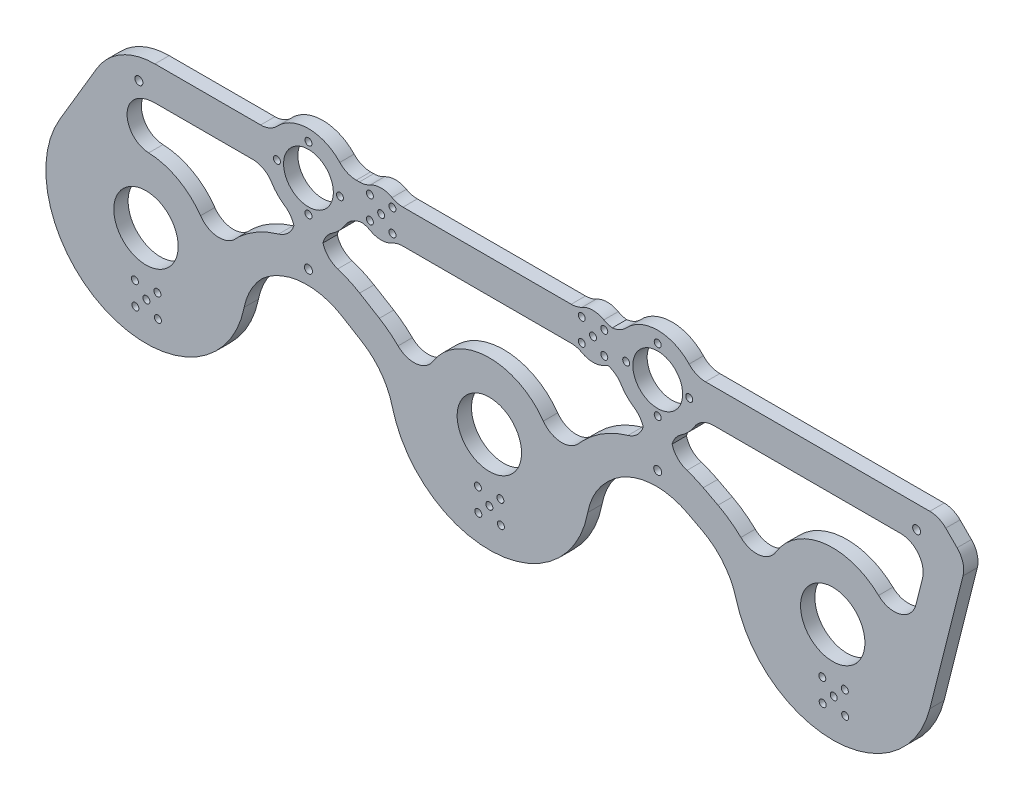
SolidWorks part; units mm, degrees
note: The reader was unsure of these and kept them because the rebuilt part matched: shared geometry of "Sketch7<4>", "Sketch10<4>".
ref_plane "Front Plane" through (0, 0, 0) normal (0, 0, 1) x (1, 0, 0)
ref_plane "Top Plane" through (0, 0, 0) normal (0, 1, 0) x (1, 0, 0)
ref_plane "Right Plane" through (0, 0, 0) normal (1, 0, 0) x (0, 0, -1)
sketch "Sketch1" plane through (0, 0, 0) normal (0, 0, 1) x (1, 0, 0)
  line L0 (0, 0) -> (43.3969, 0) construction
  line L5 (152.4, 0) -> (76.2, 0) construction
  line L6 (76.2, 0) -> (76.2, 0.75) construction
  line L7 (76.2, 0) -> (76.2, 0.75)
  line L8 (76.2, 30) -> (19.7654, -21.6122)
  line L9 (76.2, 30) -> (131.9961, -24.1854)
  line L10 (152.4, 0) -> (304.8, 0) construction
  line L11 (76.2, 0) -> (152.4, 0) construction
  line L12 (228.6, 30) -> (172.8039, -24.1854)
  line L13 (228.6, 30) -> (285.0346, -21.6122)
  line L14 (-30.661, 0) -> (-27.9755, -8.6677)
  line L15 (152.4, -3.175) -> (152.4, -32.4625) construction
  line L16 (355.6, 65) -> (332.7755, -8.6677)
  line L17 (-10.522, 65) -> (355.6, 65)
  line L18 (152.4, -53.975) -> (152.4, -87.4473) construction
  line L19 (-10.522, 65) -> (-30.661, 0)
  circle A4 centre (0, 0) radius 14.2875
  circle A5 centre (152.4, -3.175) radius 14.2875
  circle A6 centre (304.8, 0) radius 14.2875
  arc A10 (102.2191, 4.732) -> (101.6993, 0) centre (152.4, -3.175) ccw
  arc A12 (131.9961, -24.1854) -> (172.8039, -24.1854) centre (152.4, -3.7815) ccw
  arc A13 (-27.9755, -8.6677) -> (19.7654, -21.6122) centre (0, 0) ccw
  arc A14 (285.0346, -21.6122) -> (332.7755, -8.6677) centre (304.8, 0) ccw
  point P20 (0, 0)
  point P22 (-50.8, 65)
  dimension "D3" = 152.4
  dimension "D8" = 28.575
  dimension "D9" = 28.575
  dimension "D10" = 28.575
  dimension "D5" = 152.4
  dimension "D6" = 3.175
  dimension "D7" = 3.175
  dimension "D12" = 30
  dimension "D13" = 50.8
  dimension "D14" = 65
extrude "Boss-Extrude1" add sketch "Sketch1" along normal blind 6.35 contours L13 A14 L16 L17 L14 A13 L8 L9 A12 L12 A4 A5 A6
fillet "Fillet1" radius 10 2 edges at (355.6, 65, 3.175) (-10.522, 65, 3.175)
fillet "Fillet2" radius 20 2 edges at (228.6, 30, 3.175) (76.2, 30, 3.175)
sketch "Sketch2" plane through (0, 0, 0) normal (0, 0, -1) x (-1, 0, 0)
  circle A0 centre (-229.0117, 23.5185) radius 1.778
  arc A1 (-215.0781, 16.8685) -> (-242.5092, 17.2794) centre (-229.0117, 2.5208) ccw construction
  circle A2 centre (-342.0327, 55) radius 1.778
  circle A3 centre (-76.3461, 23.5185) radius 1.778
  circle A4 centre (3.1514, 55) radius 1.778
  point P5 (-228.7121, 22.5185)
  dimension "D1" = 3.556
  dimension "D3" = 3.556
  dimension "D2" = 1
extrude "Cut-Extrude1" cut sketch "Sketch2" against normal blind 6.35
fillet "Fillet4" radius 28.4734 1 edges at (-30.661, 0, 3.175)
sketch "Sketch4" plane through (0, 0, 6.35) normal (0, 0, 1) x (1, 0, 0)
  line L0 (-3.1514, 65) -> (-13.1514, 65)
  line L1 (-3.1514, 65) -> (342.0327, 65) construction
  line L2 (-3.1514, 65) -> (367.0327, 65)
  line L3 (-13.1514, 65) -> (-38.2405, 22.6598)
  line L4 (367.0327, 65) -> (347.9007, -10.8688)
  line L5 (44.45, 0) -> (68.1309, 20.9968)
  line L6 (68.1309, 20.9968) -> (107.95, -3.175)
  line L7 (196.85, -3.175) -> (220.8329, 20.772)
  line L8 (220.8329, 20.772) -> (260.35, 0)
  arc A3 (-3.1514, 65) -> (-12.7034, 57.9595) centre (-3.1514, 55) ccw construction
  circle A4 centre (0, 0) radius 44.45
  circle A5 centre (0, 0) radius 14.2875
  circle A6 centre (152.4, -3.175) radius 44.45
  circle A7 centre (304.8, 0) radius 44.45
  arc A8 (74.8883, 22.5005) -> (62.2908, 17.2794) centre (75.7883, 2.5208) ccw construction
  arc A9 (227.5763, 22.4692) -> (215.0781, 16.8685) centre (229.0117, 2.5208) ccw construction
  dimension "D1" = 25
  dimension "D4" = 88.9
  dimension "D5" = 10
  dimension "D6" = 88.9
  dimension "D7" = 88.9
extrude "Boss-Extrude2" add sketch "Sketch4" against normal up to surface (6.35 mm away)
fillet "Fillet7" radius 30 3 edges at (220.8329, 20.772, 3.175) (68.1309, 20.9968, 3.175) (-13.1514, 65, 3.175)
fillet "Fillet8" radius 30 4 edges at (260.35, 0, 3.175) (196.85, -3.175, 3.175) (107.95, -3.175, 3.175) (44.45, 0, 3.175)
sketch "Sketch5" plane through (0, 0, 6.35) normal (0, 0, 1) x (1, 0, 0)
  line L5 (247.3491, 23.7799) -> (253.8833, 20.3452)
  line L6 (247.3491, 23.7799) -> (253.8833, 20.3452)
  line L7 (333.356, -7.201) -> (347.7806, 50)
  line L8 (333.356, -7.201) -> (347.7806, 50)
  line L10 (347.7806, 50) -> (3.9432, 50)
  line L11 (-8.9613, 42.6467) -> (-25.3359, 15.0131)
  line L12 (94.8289, 22.3374) -> (103.5763, 17.0274)
  line L13 (193.7806, 14.9575) -> (194.6155, 15.7912)
  line L14 (193.7806, 14.9575) -> (194.6155, 15.7912)
  line L15 (347.7806, 50) -> (3.9432, 50)
  line L16 (-8.9613, 42.6467) -> (-25.3359, 15.0131)
  line L17 (94.8289, 22.3374) -> (103.5763, 17.0274)
  circle A1 centre (0, 0) radius 29.45
  circle A2 centre (152.4, -3.175) radius 29.45
  circle A3 centre (304.8, 0) radius 29.45
  arc A22 (3.9432, 50) -> (-8.9613, 42.6467) centre (3.9432, 35) ccw
  arc A23 (-25.3359, 15.0131) -> (28.8704, -5.8138) centre (0, 0) ccw
  arc A24 (41.2364, 17.1937) -> (28.8704, -5.8138) centre (72.9849, -14.6973) ccw
  arc A25 (94.8289, 22.3374) -> (41.2364, 17.1937) centre (71.4778, -16.1298) ccw
  arc A26 (123.85, -10.4) -> (103.5763, 17.0274) centre (80.2252, -21.4398) ccw
  arc A27 (123.85, -10.4) -> (181.3463, -8.5987) centre (152.4, -3.175) ccw
  arc A28 (193.7806, 14.9575) -> (181.3463, -8.5987) centre (225.5766, -16.8861) ccw
  arc A29 (247.3491, 23.7799) -> (194.6155, 15.7912) centre (226.4115, -16.0524) ccw
  arc A30 (276.3767, -7.7085) -> (253.8833, 20.3452) centre (232.9456, -19.4871) ccw
  arc A31 (276.3767, -7.7085) -> (333.356, -7.201) centre (304.8, 0) ccw
  arc A33 (3.9432, 50) -> (-8.9613, 42.6467) centre (3.9432, 35) ccw
  arc A34 (-25.3359, 15.0131) -> (28.8704, -5.8138) centre (0, 0) ccw
  arc A35 (41.2364, 17.1937) -> (28.8704, -5.8138) centre (72.9849, -14.6973) ccw
  arc A36 (94.8289, 22.3374) -> (41.2364, 17.1937) centre (71.4778, -16.1298) ccw
  arc A37 (123.85, -10.4) -> (103.5763, 17.0274) centre (80.2252, -21.4398) ccw
  arc A38 (123.85, -10.4) -> (181.3463, -8.5987) centre (152.4, -3.175) ccw
  arc A39 (193.7806, 14.9575) -> (181.3463, -8.5987) centre (225.5766, -16.8861) ccw
  arc A40 (247.3491, 23.7799) -> (194.6155, 15.7912) centre (226.4115, -16.0524) ccw
  arc A41 (276.3767, -7.7085) -> (253.8833, 20.3452) centre (232.9456, -19.4871) ccw
  arc A42 (276.3767, -7.7085) -> (333.356, -7.201) centre (304.8, 0) ccw
  dimension "D1" = 15
extrude "Cut-Extrude4" cut sketch "Sketch5" against normal up to surface (6.35 mm away)
fillet "Fillet9" radius 10 7 edges at (276.3767, -7.7085, 3.175) (181.3463, -8.5987, 3.175) (123.85, -10.4, 3.175) (28.8704, -5.8138, 3.175) (-25.3359, 15.0131, 3.175) (347.7806, 50, 3.175) (333.356, -7.201, 3.175)
sketch "Sketch6" plane through (0, 0, 6.35) normal (0, 0, 1) x (1, 0, 0)
  line L0 (152.4, -3.175) -> (152.4, -75.1838) construction
  circle A0 centre (72.1073, 20.164) radius 1.778
  circle A3 centre (227.1256, 20.3276) radius 1.778
  dimension "D1" = 3.556
  dimension "D2" = 3.556
extrude "Cut-Extrude5" cut sketch "Sketch6" against normal blind 10
chamfer "Chamfer1" distance 15 angle 45 1 edges at (367.0327, 65, 3.175)
fillet "Fillet11" radius 10 2 edges at (364.0119, 53.0208, 3.175) (352.0327, 65, 3.175)
sketch "Sketch7" plane through (0, 0, 6.35) normal (0, 0, 1) x (1, 0, 0)
  line L0 (152.4, -3.175) -> (152.4, -107.815) construction
  line L1 (66.1073, 37.0836) -> (65.9504, 28.5295)
  line L2 (78.1073, 37.0836) -> (78.2741, 28.354)
  arc A0 (78.1073, 37.0836) -> (66.1073, 37.0836) centre (72.1073, 55.164) ccw
  circle A1 centre (72.1073, 20.164) radius 1.778 construction
  circle A2 centre (72.1073, 55.164) radius 11.049
  circle A3 centre (72.1073, 69.1594) radius 1.55
  circle A4 centre (86.1027, 55.164) radius 1.55
  circle A5 centre (72.1073, 41.1686) radius 1.55
  circle A6 centre (58.1119, 55.164) radius 1.55
  arc A7 (94.8289, 22.3374) -> (41.2364, 17.1937) centre (71.4778, -16.1298) ccw construction
  arc A8 (78.2741, 28.354) -> (65.9504, 28.5295) centre (71.4778, -16.1298) ccw
  point P16 (72.1073, 55.164)
  line B0 (221.1256, 37.0836) -> (221.1256, 27.2622)
  line B1 (233.1256, 37.0836) -> (233.1256, 27.2622)
  arc B2 (233.1256, 37.0836) -> (221.1256, 37.0836) centre (227.1256, 55.164) ccw
  circle B3 centre (227.1256, 55.164) radius 11.049
  circle B4 centre (227.1256, 69.1594) radius 1.55
  circle B5 centre (241.121, 55.164) radius 1.55
  circle B6 centre (227.1256, 41.1686) radius 1.55
  circle B7 centre (213.1302, 55.164) radius 1.55
  arc B8 (233.1256, 27.2622) -> (221.1256, 27.2622) centre (227.1256, -17.336) ccw
  line M22 (347.8906, 65) -> (3.9432, 65)
  line M58 (3.9432, 50) -> (334.9458, 50)
  dimension "D1" = 38.1
  dimension "D3" = 22.098
  dimension "D4" = 3.1
  dimension "D2" = 35
  dimension "D5" = 13.9954
  dimension "D6" = 4
sketch_block_instance "Block1-1"
sketch_block "Block1" parameters "D1"=3.1
extrude "Boss-Extrude3" add sketch "Sketch7" against normal up to surface (6.35 mm away) up to face at (73.8853, 20.164, 0)
extrude "Cut-Extrude6" cut sketch "Sketch7<4>" against normal blind 10 contours A2 M22 M58 | A2 M58 | A2 M22 | A6 | A4 | B3 M22 M58 | B3 M22 | B3 M58 | B7 | B5
sketch "Sketch7<4>" plane through (0, 0, 6.35) normal (0, 0, 1) x (1, 0, 0) same geometry as "Sketch7"
fillet "Fillet12" radius 10 20 edges at (53.7706, 50, 3.175) (66.1073, 37.0836, 3.175) (66.0289, 32.8065, 6.35) (78.1907, 32.7188, 6.35) (78.1907, 32.7188, 0) (66.0289, 32.8065, 0) (78.1073, 37.0836, 3.175) (55.793, 65, 3.175) (65.9504, 28.5295, 3.175) (78.2741, 28.354, 3.175) (221.1256, 28.636, 3.175) (233.1256, 28.4439, 3.175) (245.4623, 50, 3.175) (221.1256, 37.0836, 3.175) (221.1256, 32.8598, 6.35) (233.1256, 32.7637, 6.35) (233.1256, 32.7637, 0) (221.1256, 32.8598, 0) (233.1256, 37.0836, 3.175) (243.4399, 65, 3.175)
sketch "Sketch8" plane through (0, 0, 6.35) normal (0, 0, 1) x (1, 0, 0)
  line L8 (151.3938, 65) -> (151.3938, 50) construction
  line L9 (202.3475, 50) -> (96.8854, 50) construction
  circle A1 centre (104.3854, 57.5) radius 1.55
  circle A2 centre (99.3854, 62.5) radius 1.55
  circle A3 centre (99.3854, 52.5) radius 1.55
  circle A4 centre (109.3854, 62.5) radius 1.55
  circle A5 centre (109.3854, 52.5) radius 1.55
  circle A6 centre (193.4021, 62.5) radius 1.55
  circle A7 centre (193.4021, 52.5) radius 1.55
  circle A8 centre (203.4021, 52.5) radius 1.55
  circle A9 centre (198.4021, 57.5) radius 1.55
  circle A10 centre (203.4021, 62.5) radius 1.55
  point P1 (104.3854, 57.5)
  point P15 (104.3854, 57.5)
  dimension "D2" = 3.1
  dimension "D3" = 3.1
  dimension "D4" = 3.1
  dimension "D5" = 3.1
  dimension "D6" = 3.1
  dimension "D1" = 10
extrude "Cut-Extrude7" cut sketch "Sketch8" against normal blind 10 contours A2 | A5 | A3 | A1 | A4 | A9 | A7 | A8 | A6 | A10
sketch "Sketch9" plane through (0, 0, 0) normal (0, 0, -1) x (-1, 0, 0)
  circle A21 centre (-304.8, 0) radius 14.2875 construction
  circle A22 centre (0, 0) radius 14.2875 construction
  circle B0 centre (-300.1643, -22.5779) radius 1.55
  circle B1 centre (-310.163, -22.4162) radius 1.55
  circle B2 centre (-305.2445, -27.4964) radius 1.55
  circle B3 centre (-310.3246, -32.4149) radius 1.55
  circle B4 centre (-300.3259, -32.5766) radius 1.55
  circle B5 centre (4.9323, -22.6142) radius 1.55
  circle B6 centre (-5.0651, -22.3872) radius 1.55
  circle B7 centre (-0.1799, -27.4994) radius 1.55
  circle B8 centre (-5.2921, -32.3846) radius 1.55
  circle B9 centre (4.7053, -32.6116) radius 1.55
  dimension "D1" = 27.5
  dimension "D2" = 27.5
sketch_block_instance "Block2-1"
sketch_block "Block2"
sketch_block_instance "Block2-2"
extrude "Cut-Extrude8" cut sketch "Sketch9" against normal blind 10
sketch "Sketch10" plane through (0, 0, 6.35) normal (0, 0, 1) x (1, 0, 0)
  circle A10 centre (0.1799, -27.4994) radius 1.55 construction
  circle A11 centre (104.3854, 57.5) radius 10
  circle A12 centre (198.4021, 57.5) radius 10
  circle A13 centre (203.4021, 62.5) radius 1.55 construction
  circle A14 centre (198.4021, 57.5) radius 1.55 construction
  circle A15 centre (193.4021, 62.5) radius 1.55 construction
  circle A16 centre (193.4021, 52.5) radius 1.55 construction
  circle A17 centre (109.3854, 52.5) radius 1.55 construction
  circle A18 centre (109.3854, 62.5) radius 1.55 construction
  circle A19 centre (99.3854, 52.5) radius 1.55 construction
  circle A20 centre (104.3854, 57.5) radius 1.55 construction
  circle A21 centre (99.3854, 62.5) radius 1.55 construction
  circle A22 centre (203.4021, 62.5) radius 1.55
  circle A23 centre (198.4021, 57.5) radius 1.55
  circle A24 centre (193.4021, 62.5) radius 1.55
  circle A25 centre (193.4021, 52.5) radius 1.55
  circle A26 centre (109.3854, 52.5) radius 1.55
  circle A27 centre (109.3854, 62.5) radius 1.55
  circle A28 centre (99.3854, 52.5) radius 1.55
  circle A29 centre (104.3854, 57.5) radius 1.55
  circle A30 centre (99.3854, 62.5) radius 1.55
  circle A31 centre (203.4021, 52.5) radius 1.55 construction
  circle A32 centre (203.4021, 52.5) radius 1.55
  circle B0 centre (157.5122, -35.5596) radius 1.55
  circle B1 centre (147.5148, -35.7866) radius 1.55
  circle B2 centre (147.2878, -25.7892) radius 1.55
  circle B3 centre (157.2852, -25.5622) radius 1.55
  circle B4 centre (152.4, -30.6744) radius 1.55
  dimension "D1" = 3.175
  dimension "D2" = 20
  dimension "D3" = 20
sketch_block_instance "Block3-1"
sketch_block "Block3"
extrude "Boss-Extrude4" add sketch "Sketch10" against normal up to surface (6.35 mm away) contours A11 A30 A29 A28 A27 A26 | A12 A32 A25 A24 A23 A22 up to face at (308.613, -22.4162, 0)
extrude "Cut-Extrude9" cut sketch "Sketch10<4>" against normal blind 10 contours B4 | B2 | B3 | B0 | B1
sketch "Sketch10<4>" plane through (0, 0, 6.35) normal (0, 0, 1) x (1, 0, 0) same geometry as "Sketch10"
fillet "Fillet13" radius 10 5 edges at (97.771, 65, 3.175) (97.771, 50, 3.175) (110.9998, 50, 3.175) (90.444, 50, 3.175) (88.4216, 65, 3.175)
fillet "Fillet14" radius 10 5 edges at (205.0165, 65, 3.175) (210.8113, 65, 3.175) (191.7877, 50, 3.175) (205.0165, 50, 3.175) (208.7889, 50, 3.175)
